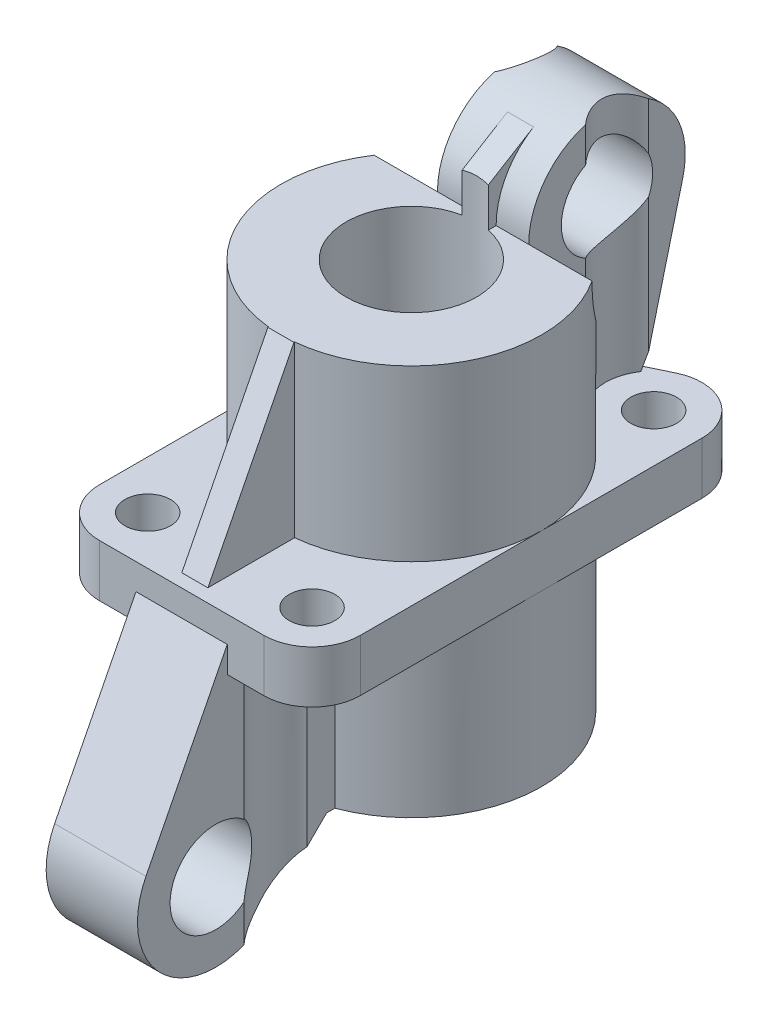
SolidWorks part; units mm, degrees
ref_plane "Front Plane" through (0, 0, 0) normal (0, 0, 1) x (1, 0, 0)
ref_plane "Top Plane" through (0, 0, 0) normal (0, 1, 0) x (1, 0, 0)
ref_plane "Right Plane" through (0, 0, 0) normal (1, 0, 0) x (0, 0, -1)
sketch "Sketch2" plane through (0, 0, 0) normal (0, 1, 0) x (1, 0, 0)
  circle A1 centre (0, 0) radius 10
  dimension "D2" = 20
extrude "Boss-Extrude1" add sketch "Sketch2" along normal mid plane 30
ref_axis "Axis1" through (0, -15, 0) along (0, 1, 0)
sketch "Sketch3" plane through (0, 0, 0) normal (1, 0, 0) x (0, 0, -1)
  line L0 (10, -15) -> (-10, -15)
  line L1 (8.3696, 20.1186) -> (0, 15)
  line L2 (-23.8501, -12.2841) -> (-10, 15)
  line L3 (0, -15) -> (0, 15) construction
  line L4 (-10, -15) -> (-14.2647, -19.25)
  line L5 (0, 15) -> (-10, 15)
  line L6 (10, 15) -> (-10, 15) construction
  line L7 (-10, 15) -> (-10, -15) construction
  line L9 (17.3119, 13.5094) -> (10, -15)
  arc A0 (-23.8501, -12.2841) -> (-14.2647, -19.25) centre (-18.5, -15) ccw
  arc A1 (17.3119, 13.5094) -> (8.3696, 20.1186) centre (11.5, 15) ccw
  circle A2 centre (11.5, 15) radius 3.5
  circle A3 centre (-18.5, -15) radius 3.5
  dimension "D1" = 7
  dimension "D2" = 7
  dimension "D3" = 6
  dimension "D4" = 6
  dimension "D6" = 15
  dimension "D5" = 11.5
  dimension "D7" = 30
  dimension "D8" = 30
  dimension "D9" = 10
extrude "Boss-Extrude2" add sketch "Sketch3" along normal mid plane 2
ref_axis "Top Crossbeam Axis" through (1, 15, -11.5) along (-1, 0, 0)
ref_axis "Bottom Crossbeam Axis" through (1, -15, 18.5) along (-1, 0, 0)
sketch "Sketch6" plane through (0, 0, 0) normal (0, 1, 0) x (1, 0, 0)
  line L0 (0, 0) -> (0, 9.572) construction
  line L1 (-4.7054, 15.6168) -> (-1, 13.8471)
  line L2 (6.3, -17.6144) -> (-6.3, -17.6144)
  line L6 (-1, 10) -> (-1, 17.3119) construction
  line L13 (10, -13.9144) -> (10, 12.278)
  line L14 (-10, -13.9144) -> (-10, 12.278)
  line L16 (-1, 13.8471) -> (1, 13.8471)
  line L22 (1, 13.8471) -> (4.7054, 15.6168)
  line L23 (0, 0) -> (9.392, 0) construction
  circle A0 centre (-6.3, 12.278) radius 1.75
  circle A1 centre (6.3, 12.278) radius 1.75
  circle A2 centre (6.3, -13.9144) radius 1.75
  circle A3 centre (-6.3, -13.9144) radius 1.75
  arc A5 (-1, 9.9499) -> (-1, -9.9499) centre (0, 0) ccw construction
  arc A6 (-4.7054, 15.6168) -> (-10, 12.278) centre (-6.3, 12.278) ccw
  arc A7 (10, 12.278) -> (4.7054, 15.6168) centre (6.3, 12.278) ccw
  arc A8 (6.3, -17.6144) -> (10, -13.9144) centre (6.3, -13.9144) ccw
  arc A9 (-10, -13.9144) -> (-6.3, -17.6144) centre (-6.3, -13.9144) ccw
  point P5 (-1, -17.6144)
  point P6 (1, 13.8471)
  dimension "D1" = 3.5
  dimension "D2" = 3.7
  dimension "D4" = 13.8
extrude "Boss-Extrude3" add sketch "Sketch6" along normal mid plane 4
sketch "Sketch9" plane through (0, 0, 0) normal (1, 0, 0) x (0, 0, -1)
  line L0 (14.36, 2) -> (17.3119, 13.5094)
  line L1 (13.8471, 0) -> (17.3119, 13.5094) construction
  line L2 (-9.9499, -15) -> (9.9499, -15) construction
  line L3 (14.36, 2) -> (5.5, 2)
  line L4 (5.5, 2) -> (5.5, 15)
  line L5 (-23.8501, -12.2841) -> (-17.6144, 0)
  line L6 (-17.6144, 0) -> (-7.9499, 0)
  line L7 (13.8471, 2) -> (9.9499, 2) construction
  line L8 (-17.6144, 0) -> (-10, 15) construction
  line L9 (-7.9499, -15) -> (-7.9499, 0)
  line L10 (-7.9499, -15) -> (-10, -15)
  line L11 (-10, -15) -> (-14.2647, -19.25)
  line L12 (0, -15) -> (0, 15) construction
  line L13 (-9.9499, -2) -> (-9.9499, -15) construction
  circle A0 centre (-18.5, -15) radius 3.5
  arc A1 (-23.8501, -12.2841) -> (-14.2647, -19.25) centre (-18.5, -15) ccw
  circle A2 centre (11.5, 15) radius 3.5
  arc A3 (17.3119, 13.5094) -> (5.5, 15) centre (11.5, 15) ccw
  arc A4 (17.3119, 13.5094) -> (8.3696, 20.1186) centre (11.5, 15) ccw construction
  circle A5 centre (11.5, 15) radius 3.5 construction
  circle A6 centre (-18.5, -15) radius 3.5 construction
  arc A7 (-23.8501, -12.2841) -> (-14.2647, -19.25) centre (-18.5, -15) ccw construction
  dimension "D1" = 10
  dimension "D2" = 2
extrude "Boss-Extrude4" add sketch "Sketch9" along normal mid plane 7
sketch "Sketch20" plane through (0, 0, 0) normal (0, 1, 0) x (1, 0, 0)
  line L1 (0, -7.7942) -> (6.75, -3.8971)
  line L2 (6.75, -3.8971) -> (6.75, 3.8971)
  line L3 (6.75, 3.8971) -> (0, 7.7942)
  line L4 (0, 7.7942) -> (-6.75, 3.8971)
  line L5 (-6.75, 3.8971) -> (-6.75, -3.8971)
  line L6 (-6.75, -3.8971) -> (0, -7.7942)
  circle A0 centre (0, 0) radius 6.75 construction
  dimension "D1" = 13.5
extrude "Cut-Extrude12" cut sketch "Sketch20" along normal blind 7.2
sketch "Sketch10" plane through (0, -15, 0) normal (0, -1, 0) x (1, 0, 0)
  line L1 (0, -7.7942) -> (6.75, -3.8971)
  line L2 (6.75, -3.8971) -> (6.75, 3.8971)
  line L3 (6.75, 3.8971) -> (0, 7.7942)
  line L4 (0, 7.7942) -> (-6.75, 3.8971)
  line L5 (-6.75, 3.8971) -> (-6.75, -3.8971)
  line L6 (-6.75, -3.8971) -> (0, -7.7942)
  circle A0 centre (0, 0) radius 6.75 construction
  dimension "D1" = 13.5
extrude "Cut-Extrude3" cut sketch "Sketch10" against normal blind 8 and the other way through all
sketch "Sketch14" plane through (-3.5, 0, 0) normal (1, 0, 0) x (0, 0, -1)
  circle A0 centre (11.5, 15) radius 6
  arc A1 (17.3119, 13.5094) -> (5.5, 15) centre (11.5, 15) ccw construction
  circle A2 centre (-18.5, -15) radius 6
  arc A5 (-12.5, -15) -> (-23.8501, -12.2841) centre (-18.5, -15) ccw construction
extrude "Cut-Extrude7" cut sketch "Sketch14" against normal through all
sketch "Sketch15" plane through (3.5, 0, 3) normal (-1, 0, 0) x (0, 0, 1)
  circle A0 centre (15.5, -15) radius 6
  circle A2 centre (-14.5, 15) radius 6
  arc A3 (11.2647, -19.25) -> (20.8501, -12.2841) centre (15.5, -15) ccw construction
  arc A6 (-8.5, 15) -> (-20.3119, 13.5094) centre (-14.5, 15) ccw construction
extrude "Cut-Extrude8" cut sketch "Sketch15" against normal through all
sketch "Sketch8" plane through (0, 15, 0) normal (0, 1, 0) x (1, 0, 0)
  circle A0 centre (0, 0) radius 5
  dimension "D1" = 10
extrude "Cut-Extrude2" cut sketch "Sketch8" against normal through all and the other way through all
sketch "Sketch16" plane through (0, 2, 0) normal (0, 1, 0) x (1, 0, 0)
  circle A0 centre (6.3, 12.278) radius 3.7
  circle A2 centre (-6.3, 12.278) radius 3.7
  arc A4 (10, 12.278) -> (4.7054, 15.6168) centre (6.3, 12.278) ccw construction
  arc A5 (-4.7054, 15.6168) -> (-10, 12.278) centre (-6.3, 12.278) ccw construction
extrude "Cut-Extrude9" cut sketch "Sketch16" along normal through all
sketch "Sketch17" plane through (0, -2, 0) normal (0, -1, 0) x (1, 0, 0)
  circle A0 centre (6.3, 13.9144) radius 3.7
  circle A1 centre (-6.3, 13.9144) radius 3.7
  arc A2 (-6.3, 17.6144) -> (-10, 13.9144) centre (-6.3, 13.9144) ccw construction
  arc A3 (10, 13.9144) -> (6.3, 17.6144) centre (6.3, 13.9144) ccw construction
  circle A4 centre (6.3, -12.278) radius 3.7
  circle A5 centre (-6.3, -12.278) radius 3.7
  arc A6 (-10, -12.278) -> (-4.7054, -15.6168) centre (-6.3, -12.278) ccw construction
  arc A7 (4.7054, -15.6168) -> (10, -12.278) centre (6.3, -12.278) ccw construction
extrude "Cut-Extrude10" cut sketch "Sketch17" along normal through all
sketch "Sketch21" plane through (0, 0, 0) normal (1, 0, 0) x (0, 0, -1)
  circle A0 centre (11.5, 15) radius 3.5
  arc A1 (14.6967, 16.4252) -> (9.8594, 18.0916) centre (11.5, 15) ccw construction
extrude "Cut-Extrude13" cut sketch "Sketch21" against normal through all and the other way through all
equation "\"CrossbarVSep\"=\"D8@Sketch3\""
equation "\"CrossbarHSep\"=\"D7@Sketch3\""
equation "\"CrossbarOffset\"=\"D5@Sketch3\""
